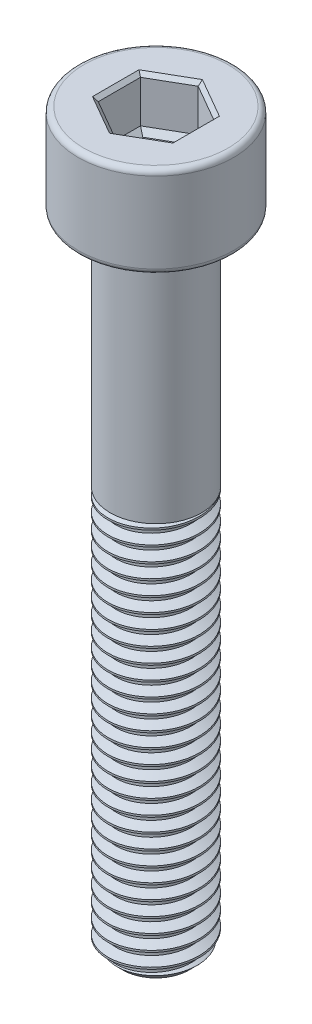
SolidWorks part; units mm, degrees
material "AISI Type A2 Tool Steel"
ref_plane "Front Plane" through (0, 0, 0) normal (0, 0, 1) x (1, 0, 0)
ref_plane "Top Plane" through (0, 0, 0) normal (0, 1, 0) x (1, 0, 0)
ref_plane "Right Plane" through (0, 0, 0) normal (1, 0, 0) x (0, 0, -1)
sketch "Sketch1" plane through (0, 0, 0) normal (0, 1, 0) x (1, 0, 0)
  circle A0 centre (0, 0) radius 2.5
  dimension "D1" = 5
extrude "Boss-Extrude1" add sketch "Sketch1" along normal blind 22
thread "Thread1" pitch 0.8 method cut profile "Thread Profile1" start angle 0, offset 1, length 0, pitch 0.8, diameter 5
ref_plane "Plane1" through (-2.5, 23, 0) normal (0, 0, 1) x (-1, 0, 0)
sketch "Thread Profile1" plane through (-2.5, 23, 0) normal (0, 0, 1) x (-1, 0, 0)
  line L0 (0, 0) -> (0, 0.8) construction
  line L11 (0, 0) -> (0, 0.7)
  line L12 (0, 0.7) -> (-0.433, 0.45)
  line L13 (-0.433, 0.45) -> (-0.433, 0.25)
  line L15 (-0.433, 0.25) -> (0, 0)
  line L17 (-0.433, 0.35) -> (0, 0.35) construction
  point P2 (0, 0)
  dimension "Pitch" = 0.8
  dimension "Profile_Angle" = 60
  dimension "Profile_Land" = 0.2
  dimension "Profile_Height" = 0.433
sketch "Sketch2" plane through (0, 22, 0) normal (0, 1, 0) x (1, 0, 0)
  circle A0 centre (0, 0) radius 2.5
  dimension "D1" = 5
extrude "Boss-Extrude2" add sketch "Sketch2" along normal blind 13
sketch "Sketch3" plane through (0, 35, 0) normal (0, 1, 0) x (1, 0, 0)
  circle A0 centre (0, 0) radius 4.25
  dimension "D1" = 8.5
extrude "Boss-Extrude3" add sketch "Sketch3" along normal blind 5
fillet "Fillet1" radius 0.3 2 edges at (0, 35, 4.25) (0, 40, 4.25)
sketch "Sketch4" plane through (0, 0, 0) normal (0, 0, 1) x (1, 0, 0)
  line L0 (0, 0) -> (0, 0.4416) construction
  line L1 (0, 0) -> (2.51, 0) construction
  line L2 (2.51, 0) -> (2.51, 0.7)
  line L3 (2.51, 0.7) -> (1.81, 0)
  line L4 (1.81, 0) -> (2.51, 0)
  dimension "D1" = 0.7
  dimension "D2" = 45
  dimension "D3" = 2.51
revolve "Cut-Revolve1" cut sketch "Sketch4" angle 360 about L0
sketch "Sketch5" plane through (0, 40, 0) normal (0, 1, 0) x (1, 0, 0)
  line L1 (0, 2.3094) -> (-2, 1.1547)
  line L2 (-2, 1.1547) -> (-2, -1.1547)
  line L3 (-2, -1.1547) -> (0, -2.3094)
  line L4 (0, -2.3094) -> (2, -1.1547)
  line L5 (2, -1.1547) -> (2, 1.1547)
  line L6 (2, 1.1547) -> (0, 2.3094)
  circle A0 centre (0, 0) radius 2 construction
  dimension "D1" = 4
extrude "Cut-Extrude1" cut sketch "Sketch5" against normal blind 2.5
chamfer "Chamfer1" distance 0.2 angle 45 6 edges at (-1, 40, 1.7321) (1, 40, 1.7321) (2, 40, 0) (1, 40, -1.7321) (-1, 40, -1.7321) (-2, 40, 0)
sketch "Sketch6" plane through (0, 37.5, 0) normal (0, 1, 0) x (1, 0, 0)
  line L1 (0, 2.3094) -> (-2, 1.1547)
  line L2 (-2, 1.1547) -> (-2, -1.1547)
  line L3 (-2, -1.1547) -> (0, -2.3094)
  line L4 (0, -2.3094) -> (2, -1.1547)
  line L5 (2, -1.1547) -> (2, 1.1547)
  line L6 (2, 1.1547) -> (0, 2.3094)
  circle A0 centre (0, 0) radius 2 construction
extrude "Cut-Extrude2" cut sketch "Sketch6" against normal blind 0.3 draft 45
